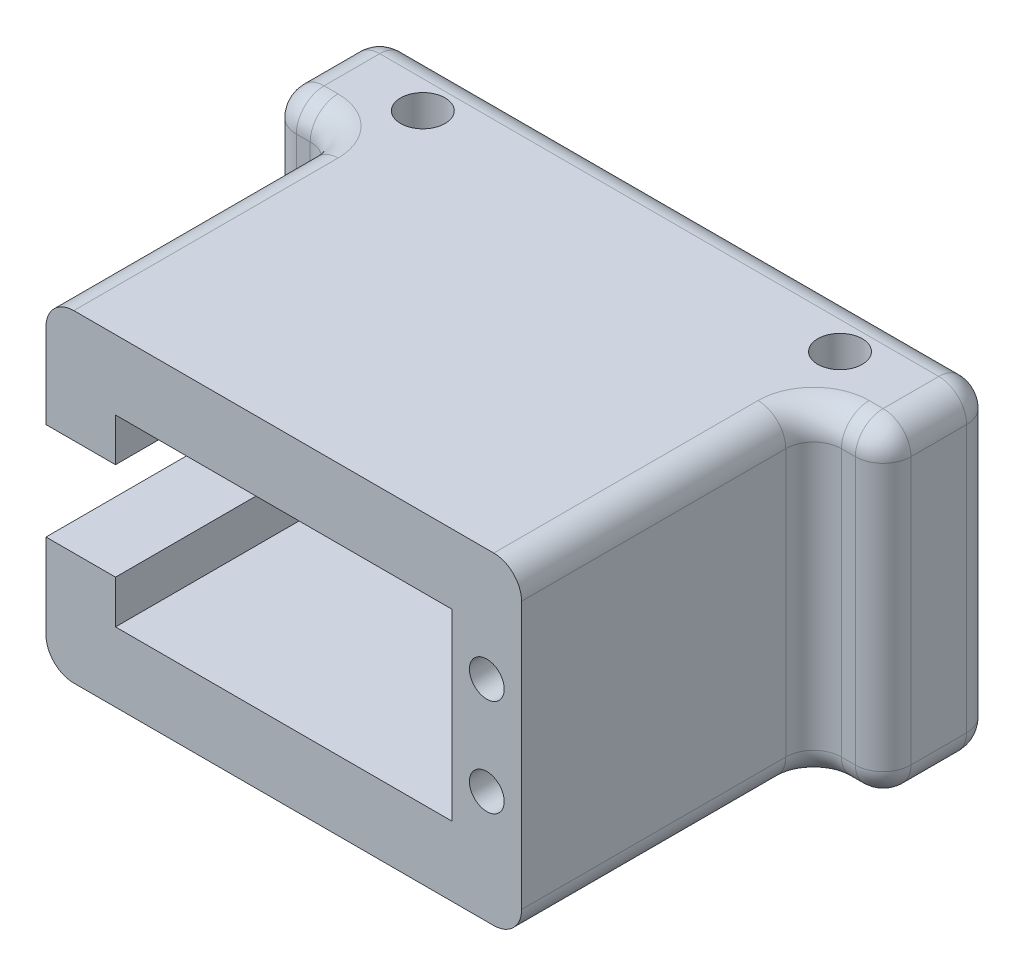
SolidWorks part; units mm, degrees
material "PETG"
ref_plane "Front Plane" through (0, 0, 0) normal (0, 0, 1) x (1, 0, 0)
ref_plane "Top Plane" through (0, 0, 0) normal (0, 1, 0) x (1, 0, 0)
ref_plane "Right Plane" through (0, 0, 0) normal (1, 0, 0) x (0, 0, -1)
sketch "Sketch2" plane through (0, 0, 0) normal (0, 0, 1) x (1, 0, 0)
  line L0 (-17.1, -11.6) -> (-17.1, 11.6)
  line L1 (-12.1, -6.6) -> (12.1, -6.6)
  line L2 (-12.1, -6.6) -> (-12.1, 6.6)
  line L3 (-12.1, 6.6) -> (12.1, 6.6)
  line L4 (12.1, -6.6) -> (12.1, 6.6)
  line L5 (-12.1, -6.6) -> (12.1, 6.6) construction
  line L6 (-12.1, 6.6) -> (12.1, -6.6) construction
  line L7 (-17.1, 11.6) -> (17.1, 11.6)
  line L8 (17.1, -11.6) -> (17.1, 11.6)
  line L9 (-17.1, -11.6) -> (17.1, -11.6)
  point P0 (0, 0)
  dimension "D2" = 24.2
  dimension "D3" = 13.2
  dimension "D1" = 5
extrude "Boss-Extrude1" add sketch "Sketch2" along normal blind 21
extrude "Boss-Extrude2" add sketch "Sketch2<2>" against normal blind 8 contours L1 L4 L3 L2 | L0 L9 L8 L7 L4 L1 L2 L3 region at (-16.6867, 0, 0) region at (0, 0, 0)
sketch "Sketch2<2>" plane through (0, 0, 0) normal (0, 0, 1) x (1, 0, 0) same geometry as "Sketch2"
sketch "Sketch3" plane through (0, -11.6, 0) normal (0, -1, 0) x (1, 0, 0)
  line L0 (-17.1, -4) -> (17.1, -4) construction
  line L1 (0, 0) -> (0, -8) construction
  line L4 (-17.1, 21) -> (-17.1, -8)
  line L5 (-17.1, -8) -> (17.1, -8)
  line L6 (17.1, -8) -> (17.1, 21)
  line L7 (17.1, 21) -> (-17.1, 21)
  line L8 (-17.1, 21) -> (-17.1, -8)
  line L9 (-17.1, -8) -> (17.1, -8)
  line L10 (17.1, -8) -> (17.1, 21)
  line L11 (17.1, 21) -> (-17.1, 21)
  circle A0 centre (-15, -4) radius 1.6
  circle A1 centre (15, -4) radius 1.6
  dimension "D2" = 3.2
  dimension "D3" = 30
  dimension "D4" = 4
  dimension "D1" = 0
sketch "Sketch4" plane through (0, -11.6, 0) normal (0, -1, 0) x (1, 0, 0)
  line L0 (12.1, 0) -> (-12.1, 0) construction
  line L1 (12.1, 0) -> (-12.1, 0)
  line L2 (-12.1, 0) -> (-22.1, 0)
  line L3 (-17.1, -8) -> (17.1, -8) construction
  line L4 (-17.1, -8) -> (17.1, -8)
  line L5 (-22.1, 0) -> (-22.1, -8)
  line L6 (-22.1, -8) -> (-17.1, -8)
  line L7 (0, 0) -> (0, -8) construction
  line L8 (22.1, -8) -> (17.1, -8)
  line L9 (22.1, 0) -> (22.1, -8)
  line L10 (12.1, 0) -> (22.1, 0)
  dimension "D1" = 10
extrude "Boss-Extrude3" add sketch "Sketch4" against normal up to surface (23.2 mm away) up to face at (0, 11.6, 6.5)
extrude "Cut-Extrude1" cut sketch "Sketch3" against normal through all contours A0 | A1 region at (-15, -11.6, -4) region at (15, -11.6, -4)
fillet "Fillet1" radius 2 20 edges at (19.6, 11.6, 0) (19.6, -11.6, 0) (-19.6, 11.6, 0) (-19.6, -11.6, 0) (17.1, 11.6, 10.5) (17.1, 0, 0) (17.1, -11.6, 10.5) (22.1, 0, -8) (22.1, -11.6, -4) (22.1, 0, 0) (22.1, 11.6, -4) (0, -11.6, -8) (0, 11.6, -8) (-22.1, 11.6, -4) (-22.1, -11.6, -4) (-17.1, 11.6, 10.5) (-17.1, -11.6, 10.5) (-22.1, 0, 0) (-22.1, 0, -8) (-17.1, 0, 0)
sketch "Sketch5" plane through (0, 0, 21) normal (0, 0, 1) x (1, 0, 0)
  line L0 (-12.1, 0) -> (-17.1, 0) construction
  line L1 (-12.1, 6.6) -> (-12.1, -6.6) construction
  line L2 (-17.1, 9.6) -> (-17.1, -9.6) construction
  line L3 (-17.1, 3.5) -> (-12.1, 3.5)
  line L4 (-17.1, 9.6) -> (-17.1, -9.6) construction
  line L5 (-12.1, 6.6) -> (-12.1, -6.6) construction
  line L6 (-17.1, -3.5) -> (-12.1, -3.5)
  line L7 (-12.1, 3.5) -> (-12.1, -3.5)
  line L8 (-17.1, 3.5) -> (-17.1, -3.5)
  dimension "D1" = 7
  dimension "D2" = 3.5
extrude "Cut-Extrude2" cut sketch "Sketch5" against normal up to vertex (19 mm away) up to point (-17.1, 9.6, 2)
sketch "Sketch6" plane through (0, 0, 21) normal (0, 0, 1) x (1, 0, 0)
  line L0 (12.1, 0) -> (17.1, 0) construction
  line L2 (12.1, -6.6) -> (12.1, 6.6) construction
  line L3 (17.1, -9.6) -> (17.1, 9.6) construction
  line L4 (14.6, 4.3274) -> (14.6, -3.4307) construction
  circle A0 centre (14.6, 3.5) radius 1.25
  circle A1 centre (14.6, -3.5) radius 1.25
  dimension "D2" = 7
  dimension "D3" = 2.5
  dimension "D1" = 2.5
extrude "Cut-Extrude3" cut sketch "Sketch6" against normal blind 6
equation "\"D2@Sketch2\"=23+1.2"
equation "\"D2@Sketch5\"=\"D1@Sketch5\"/2"
